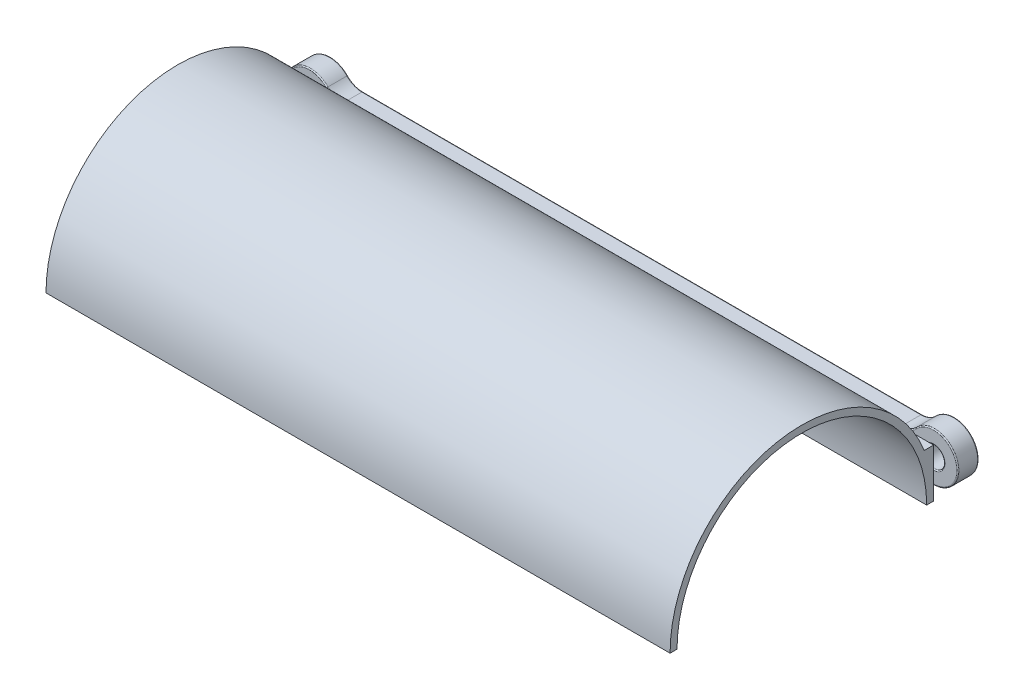
SolidWorks part; units mm, degrees
ref_plane "Front Plane" through (0, 0, 0) normal (0, 0, 1) x (1, 0, 0)
ref_plane "Top Plane" through (0, 0, 0) normal (0, 1, 0) x (1, 0, 0)
ref_plane "Right Plane" through (0, 0, 0) normal (1, 0, 0) x (0, 0, -1)
sketch "Sketch1" plane through (0, 0, 0) normal (0, 0, 1) x (1, 0, 0)
  line L0 (0, 0) -> (90, 0) construction
  line L1 (0, 3.5) -> (90, 3.5) construction
  line L2 (0, -3.5) -> (90, -3.5) construction
  line L3 (45, 0) -> (45, -3.5) construction
  line L5 (3.1623, -1.5) -> (86.8377, -1.5)
  line L6 (3.1623, -1.5) -> (3.1623, 1.5) construction
  line L7 (3.1623, 1.5) -> (86.8377, 1.5)
  line L8 (86.8377, -1.5) -> (86.8377, 1.5) construction
  line L9 (3.1623, -1.5) -> (86.8377, 1.5) construction
  line L10 (3.1623, 1.5) -> (86.8377, -1.5) construction
  arc A0 (0, 3.5) -> (0, -3.5) centre (0, 0) ccw construction
  arc A1 (90, -3.5) -> (90, 3.5) centre (90, 0) ccw construction
  circle A2 centre (0, 0) radius 3.5
  circle A3 centre (0, 0) radius 1.5
  circle A4 centre (90, 0) radius 1.5
  circle A5 centre (90, 0) radius 3.5
  point P3 (45, 0)
  dimension "D3" = 3
  dimension "D1" = 7
  dimension "D2" = 90
  dimension "D4" = 3
extrude "Boss-Extrude1" add sketch "Sketch1" along normal mid plane 3 contours A2 A3 | L5 A5 L7 A2 | A5 A4 region at (45, 0, 0) region at (-3.401, 0, 0) region at (86.599, 0, 0)
fillet "Fillet1" radius 3 4 edges at (3.1623, -1.5, 0) (86.8377, -1.5, 0) (86.8377, 1.5, 0) (3.1623, 1.5, 0)
fillet "Fillet2" radius 0.15 20 edges at (91.5, 0, -1.5) (1.5, 0, -1.5) (3.5137, -1.7404, -1.5) (45, -1.5, -1.5) (86.4863, -1.7404, -1.5) (93.5, 0, -1.5) (86.4863, 1.7404, -1.5) (45, 1.5, -1.5) (3.5137, 1.7404, -1.5) (-3.5, 0, -1.5) (91.5, 0, 1.5) (1.5, 0, 1.5) (86.4863, 1.7404, 1.5) (93.5, 0, 1.5) (86.4863, -1.7404, 1.5) (45, -1.5, 1.5) (3.5137, -1.7404, 1.5) (-3.5, 0, 1.5) (3.5137, 1.7404, 1.5) (45, 1.5, 1.5)
ref_plane "基准面1" through (0, 0, 0) normal (0, -1, 0) x (-1, 0, 0)
sketch "草图5" plane through (0, 0, 1.5) normal (0, 0, 1) x (1, 0, 0)
  circle A0 centre (80.7816, 0) radius 0.422
sketch "草图6" plane through (0, 0, 1.5) normal (0, 0, 1) x (1, 0, 0)
  line L0 (84.74, 0) -> (103.74, 0)
  line L1 (-3.208, 0) -> (3.208, 0) construction
  line L2 (84.74, 0) -> (84.74, 3.2567)
  dimension "D1" = 19
ref_plane "基准面2" through (84.74, 0, 0) normal (1, 0, 0) x (0, 1, 0)
ref_plane "基准面3" through (103.74, 0, 0) normal (1, 0, 0) x (0, 0, -1)
ref_plane "基准面4" through (0, 0, -1.5) normal (0, 0, -1) x (-1, 0, 0)
ref_axis "基准轴1" through (103.74, 0, 5.2023) along (0, 0, -1)
ref_axis "基准轴2" through (103.74, -3.5175, -1.5) along (0, 1, 0)
ref_point "点1"
sketch "草图8" plane through (0, 0, 1.5) normal (0, 0, 1) x (1, 0, 0)
  line L0 (90, 0) -> (90, -5.5)
  dimension "D1" = 5.5
sketch "草图9" plane through (0, 0, -1.5) normal (0, 0, -1) x (-1, 0, 0)
  line L0 (-90, -5.5) -> (-90, 0)
ref_plane "基准面5" through (90, 0, 0) normal (1, 0, 0) x (0, 0, -1)
sketch "草图10" plane through (90, 0, 0) normal (1, 0, 0) x (0, 0, -1)
  line L0 (-1.5, -5.5) -> (-2.5, -5.5)
  line L1 (-1.5, 0) -> (-1.5, -5.5) construction
  line L2 (-39.5, -5.5) -> (-38.5, -5.5)
  line L13 (-1.5, 1.5) -> (-1.5, -5.5)
  line L14 (-2.8365, 1.5) -> (-1.5, 1.5)
  arc A1 (-2.5, -5.5) -> (-38.5, -5.5) centre (-20.5, -5.5) ccw
  arc A3 (-2.8365, 1.5) -> (-39.5, -5.5) centre (-20.5, -5.5) ccw
  dimension "D1" = 19
sketch "草图11" plane through (0, 0, 1.5) normal (0, 0, 1) x (1, 0, 0)
  line L0 (0, 0) -> (0, 1.2366)
sketch "草图12" plane through (0, 0, -1.5) normal (0, 0, -1) x (-1, 0, 0)
  line L0 (0, 0) -> (0, 1.2366)
ref_plane "基准面6" through (0, 0, 0) normal (1, 0, 0) x (0, 0, -1)
extrude "凸台-拉伸2" add sketch "草图10" against normal up to surface (90 mm away) up to plane "基准面6"
